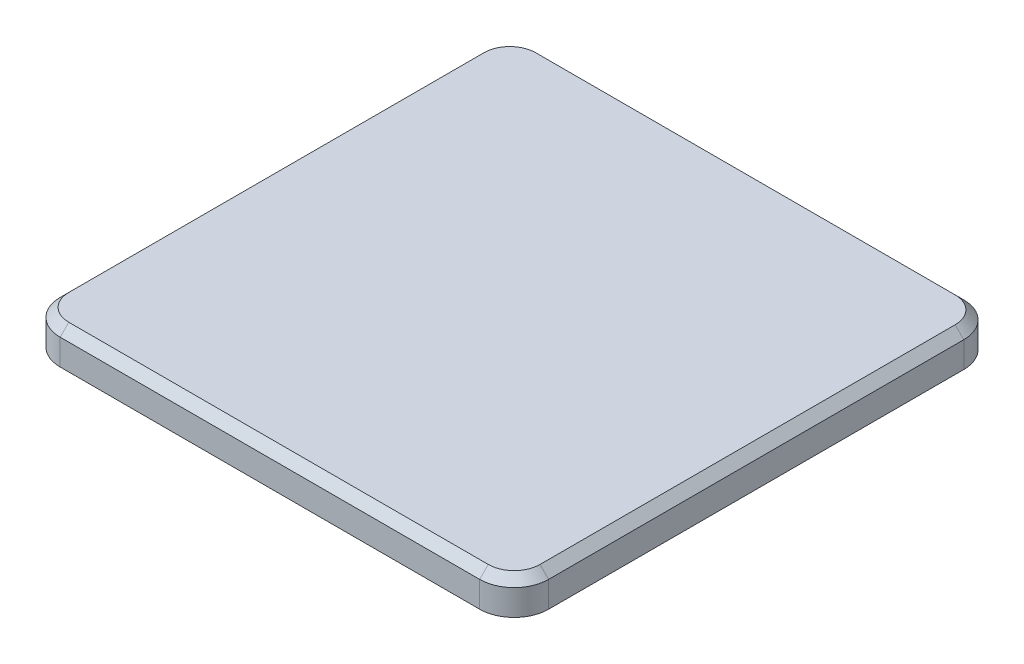
SolidWorks part; units mm, degrees
ref_plane "Front Plane" through (0, 0, 0) normal (0, 0, 1) x (1, 0, 0)
ref_plane "Top Plane" through (0, 0, 0) normal (0, 1, 0) x (1, 0, 0)
ref_plane "Right Plane" through (0, 0, 0) normal (1, 0, 0) x (0, 0, -1)
sketch "Sketch1" plane through (0, 0, 0) normal (0, 1, 0) x (1, 0, 0)
  line L0 (42.5, -42.125) -> (42.5, 42.125)
  line L1 (39.5, -39.125) -> (-39.5, -39.125)
  line L2 (39.5, -39.125) -> (39.5, 39.125)
  line L3 (39.5, 39.125) -> (-39.5, 39.125)
  line L4 (-39.5, -39.125) -> (-39.5, 39.125)
  line L5 (39.5, -39.125) -> (-39.5, 39.125) construction
  line L6 (39.5, 39.125) -> (-39.5, -39.125) construction
  line L7 (42.5, 42.125) -> (-42.5, 42.125)
  line L8 (-42.5, -42.125) -> (-42.5, 42.125)
  line L9 (42.5, -42.125) -> (-42.5, -42.125)
  point P0 (0, 0)
  dimension "D2" = 78.25
  dimension "D3" = 79
  dimension "D1" = 3
extrude "Boss-Extrude1" add sketch "Sketch1" along normal blind 3
extrude "Boss-Extrude2" add sketch "Sketch1<2>" along normal blind 3 from surface contours L9 L0 L7 L8 L1 L4 L3 L2 | L4 L1 L2 L3 region at (0, 0, 40.9282) region at (0, 0, 0) starting at face at (0, 3, 0)
sketch "Sketch1<2>" plane through (0, 0, 0) normal (0, 1, 0) x (1, 0, 0) same geometry as "Sketch1"
fillet "Fillet1" radius 3 4 edges at (39.5, 1.5, -39.125) (39.5, 1.5, 39.125) (-39.5, 1.5, -39.125) (-39.5, 1.5, 39.125)
fillet "Fillet2" radius 6 4 edges at (42.5, 3, 42.125) (42.5, 3, -42.125) (-42.5, 3, -42.125) (-42.5, 3, 42.125)
chamfer "Chamfer1" distance 1.5 angle 45 8 edges at (0, 6, -42.125) (40.7426, 6, -40.3676) (-40.7426, 6, -40.3676) (42.5, 6, 0) (-42.5, 6, 0) (40.7426, 6, 40.3676) (-40.7426, 6, 40.3676) (0, 6, 42.125)
